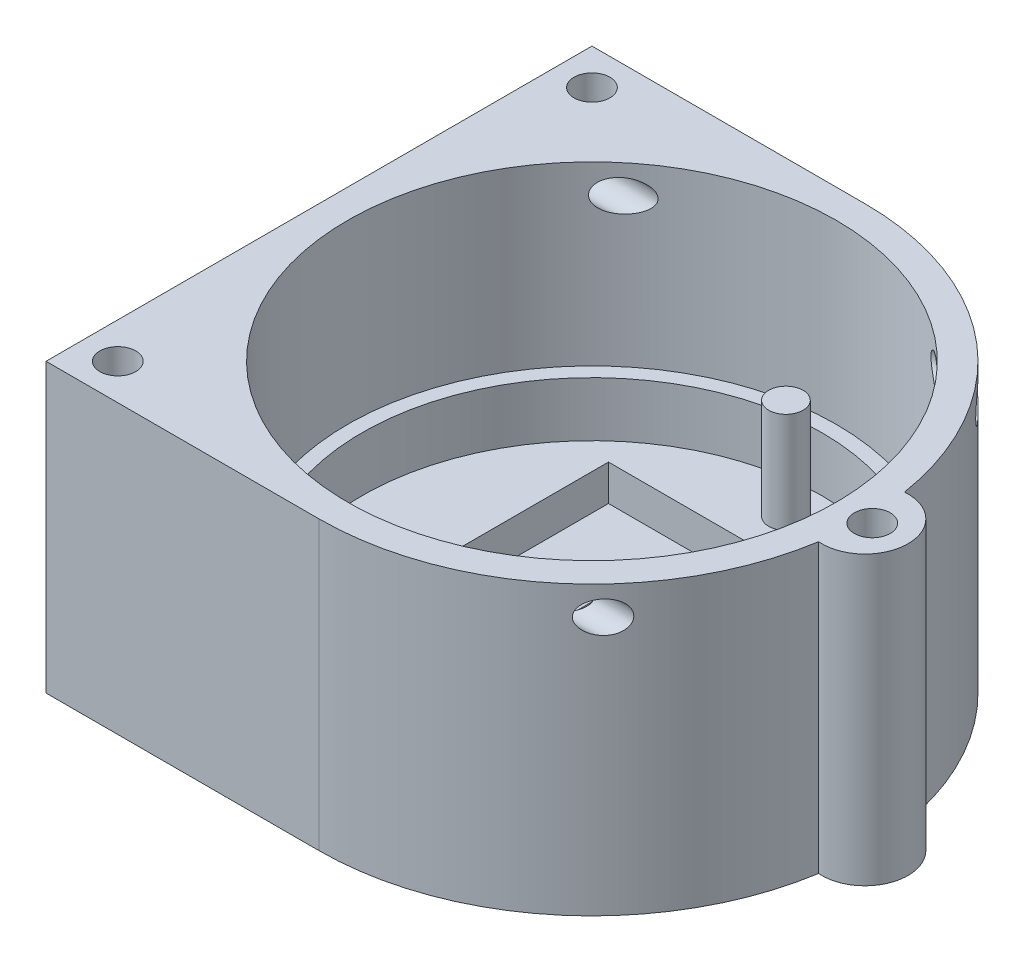
SolidWorks part; units mm, degrees
ref_plane "Front Plane" through (0, 0, 0) normal (0, 0, 1) x (1, 0, 0)
ref_plane "Top Plane" through (0, 0, 0) normal (0, 1, 0) x (1, 0, 0)
ref_plane "Right Plane" through (0, 0, 0) normal (1, 0, 0) x (0, 0, -1)
sketch "Sketch3" plane through (0, 0, 0) normal (0, 1, 0) x (1, 0, 0)
  line L1 (0, 19) -> (-19, 19)
  line L3 (0, -19) -> (-19, -19)
  line L4 (-19, 19) -> (-19, -19)
  arc A0 (18.7632, 2.9906) -> (0, 19) centre (0, 0) ccw
  arc A1 (0, -19) -> (18.7632, -2.9906) centre (0, 0) ccw
  arc A2 (18.7632, -2.9906) -> (18.7632, 2.9906) centre (19, 0) ccw
  point P3 (19, 0)
  point P10 (18.7632, -2.9906)
  dimension "D1" = 19
  dimension "D4" = 19
  dimension "D3" = 3
  dimension "D2" = 19
  dimension "D5" = 19
extrude "Main Body" add sketch "Sketch3" against normal blind 20
sketch "Sketch5" plane through (0, -20, 0) normal (0, -1, 0) x (1, 0, 0)
  circle A0 centre (0, 0) radius 17
  arc A2 (18.7632, 2.9906) -> (0, 19) centre (0, 0) ccw construction
  dimension "D1" = 2
extrude "Cut for Headers" cut sketch "Sketch5" against normal through all from offset 7.7 offset against normal yes
ref_axis "Central Axis" through (0, 1, 0) along (0, -1, 0)
ref_axis "Horizontal Axis" through (-20.9, 0, 0) along (1, 0, 0)
ref_axis "Vertical Axis" through (0, 0, -20.9) along (0, 0, 1)
sketch "Sketch7" plane through (0, 0, 0) normal (1, 0, 0) x (0, 0, -1)
  circle A0 centre (0, 0) radius 7
  point P3 (0, -3.3432)
  dimension "D1" = 14
extrude "Cut for ADNS Wires" [suppressed] cut sketch "Sketch7" along normal up to next
sketch "Sketch8" plane through (0, -12.3, 0) normal (0, 1, 0) x (1, 0, 0)
  circle A0 centre (0, 0) radius 16
  dimension "D1" = 32
  dimension "D2" = 0
extrude "Cut for PCB" cut sketch "Sketch8" against normal blind 3.8
sketch "Sketch9" plane through (0, -16.1, 0) normal (0, 1, 0) x (1, 0, 0)
  line L0 (0, 16) -> (0, -16) construction
  line L1 (-16, 0) -> (16, 0) construction
  circle A1 centre (0, 0) radius 16 construction
  circle A2 centre (0, 13.5) radius 1.2
  circle A3 centre (0, -13.5) radius 1.2
  point P0 (0, 0)
  dimension "D1" = 2.4
  dimension "D2" = 27
extrude "Cut for PCB Screw Holes" [suppressed] cut sketch "Sketch9" against normal blind 5
sketch "Sketch10" plane through (0, -16.1, 0) normal (0, 1, 0) x (1, 0, 0)
  line L1 (-9.45, -10.6) -> (9.45, -10.6)
  line L2 (-9.45, -10.6) -> (-9.45, 10.6)
  line L3 (-9.45, 10.6) -> (9.45, 10.6)
  line L4 (9.45, -10.6) -> (9.45, 10.6)
  line L5 (-9.45, -10.6) -> (9.45, 10.6) construction
  line L6 (-9.45, 10.6) -> (9.45, -10.6) construction
  point P0 (0, 0)
  dimension "D1" = 18.9
  dimension "D2" = 21.2
extrude "Cut for Lens" cut sketch "Sketch10" against normal blind 2.5
sketch "Sketch11" plane through (0, -18.6, 0) normal (0, 1, 0) x (1, 0, 0)
  line L1 (-4.1, -5.1) -> (4.1, -5.1)
  line L2 (-4.1, -5.1) -> (-4.1, 5.1)
  line L3 (-4.1, 5.1) -> (4.1, 5.1)
  line L4 (4.1, -5.1) -> (4.1, 5.1)
  line L5 (-4.1, -5.1) -> (4.1, 5.1) construction
  line L6 (-4.1, 5.1) -> (4.1, -5.1) construction
  point P0 (0, 0)
  dimension "D1" = 10.2
  dimension "D2" = 8.2
extrude "Cut for Pupil" cut sketch "Sketch11" against normal up to next
sketch "Sketch13" plane through (0, 0, 0) normal (1, 0, 0) x (0, 0, -1)
  line L0 (0, 1) -> (0, -21) construction
  line L1 (20.9, 0) -> (-20.9, 0) construction
  circle A0 centre (13, -2) radius 1.1
  circle A1 centre (-13, -2) radius 1.1
  point P0 (13, -2)
  point P7 (-13, -2)
  dimension "D3" = 2.2
  dimension "D4" = 13
  dimension "D5" = 2.2
  dimension "D1" = 13
  dimension "D2" = 2
extrude "Cuts for Body Screw Holes" cut sketch "Sketch13" against normal through all both and the other way through all
ref_plane "Right Face" through (-19, 0, 0) normal (1, 0, 0) x (0, 0, -1)
sketch "Sketch14" plane through (0, 0, 0) normal (0, 1, 0) x (1, 0, 0)
  line L0 (18.7632, 2.9906) -> (18.7632, -2.9906) construction
  line L1 (22, 0) -> (-19.2021, 0) construction
  line L2 (0, 19) -> (-19, 19) construction
  line L3 (-19, -11) -> (-19, 11) construction
  arc A0 (18.7632, -2.9906) -> (18.7632, 2.9906) centre (19, 0) ccw construction
  circle A1 centre (19.5132, 0) radius 1.25
  circle A2 centre (-16.5, 16.5) radius 1.25
  circle A3 centre (-16.5, -16.5) radius 1.25
  point P11 (18.7632, 0)
  point P12 (19.5132, 0)
  dimension "D2" = 2.5
  dimension "D3" = 2.5
  dimension "D1" = 0.75
  dimension "D4" = 2.5
  dimension "D5" = 2.5
extrude "Cut for Top Screw Holes" cut sketch "Sketch14" against normal blind 7
sketch "Sketch15" [suppressed] plane through (0, -16.1, 0) normal (0, 1, 0) x (1, 0, 0)
  circle A0 centre (0, 13.5) radius 2.25
  circle A1 centre (0, -13.5) radius 2.25
  dimension "D1" = 4.5
  dimension "D2" = 4.5
extrude "Extrusion for PCB Screw Support" [suppressed] add sketch "Sketch15" along normal blind 1.2
extrude "Extrusion for Holding PCB" add sketch "Sketch9<2>" along normal blind 7
sketch "Sketch9<2>" plane through (0, -16.1, 0) normal (0, 1, 0) x (1, 0, 0) same geometry as "Sketch9"
